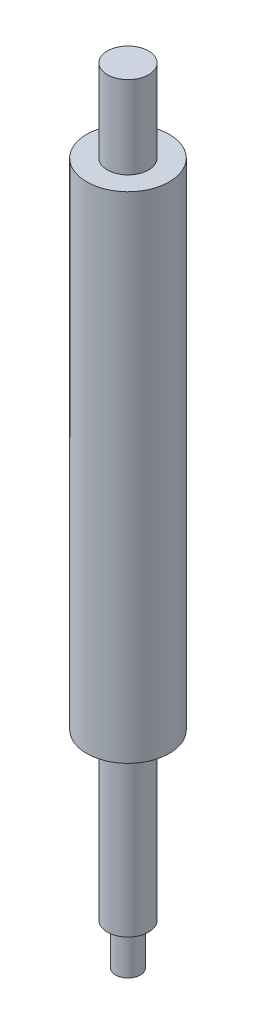
SolidWorks part; units mm, degrees
ref_plane "Plan de face" through (0, 0, 0) normal (0, 0, 1) x (1, 0, 0)
ref_plane "Plan de dessus" through (0, 0, 0) normal (0, 1, 0) x (1, 0, 0)
ref_plane "Plan de droite" through (0, 0, 0) normal (1, 0, 0) x (0, 0, -1)
sketch "Esquisse1" plane through (0, 0, 0) normal (0, 0, 1) x (1, 0, 0)
  line L0 (2.5, 5) -> (1.5, 5)
  line L1 (2.5, 5) -> (2.5, 25)
  line L2 (2.5, 25) -> (5, 25)
  line L3 (5, 25) -> (5, 85)
  line L4 (5, 85) -> (2.5, 85)
  line L5 (2.5, 85) -> (2.5, 95)
  line L6 (2.5, 95) -> (0, 95)
  line L7 (0, 95) -> (0, 0)
  line L8 (1.5, 5) -> (1.5, 0)
  line L9 (1.5, 0) -> (0, 0)
  point P9 (0, 0)
  point P12 (1.5, 2.5)
  dimension "D1" = 2.5
  dimension "D2" = 5
  dimension "D3" = 20
  dimension "D4" = 10
  dimension "D5" = 5
  dimension "D6" = 1.5
  dimension "D7" = 95
revolve "Révolution1" add sketch "Esquisse1" angle 360 about L7
